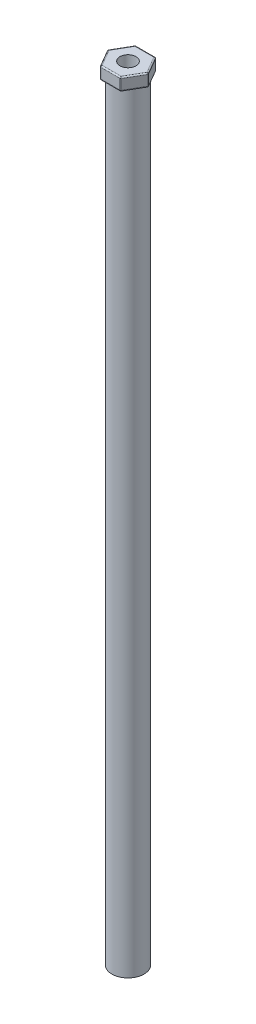
SolidWorks part; units mm, degrees
ref_plane "Front Plane" through (0, 0, 0) normal (0, 0, 1) x (1, 0, 0)
ref_plane "Top Plane" through (0, 0, 0) normal (0, 1, 0) x (1, 0, 0)
ref_plane "Right Plane" through (0, 0, 0) normal (1, 0, 0) x (0, 0, -1)
sketch "Sketch1" plane through (0, 0, 0) normal (0, 1, 0) x (1, 0, 0)
  circle A0 centre (0, 0) radius 6.35
  circle A1 centre (0, 0) radius 3.175
  dimension "D1" = 12.7
extrude "Boss-Extrude1" add sketch "Sketch1" along normal blind 304.8
ref_plane "Plane1" through (0, 152.4, 0) normal (0, 1, 0) x (1, 0, 0)
sketch "Sketch2" plane through (0, 304.8, 0) normal (0, 1, 0) x (1, 0, 0)
  line L1 (-8.0656, 0) -> (-4.0328, -6.985)
  line L2 (-4.0328, -6.985) -> (4.0328, -6.985)
  line L3 (4.0328, -6.985) -> (8.0656, 0)
  line L4 (8.0656, 0) -> (4.0328, 6.985)
  line L5 (4.0328, 6.985) -> (-4.0328, 6.985)
  line L6 (-4.0328, 6.985) -> (-8.0656, 0)
  circle A0 centre (0, 0) radius 6.985 construction
  circle A1 centre (0, 0) radius 3.175
  dimension "D1" = 13.97
extrude "Boss-Extrude2" add sketch "Sketch2" along normal blind 5
fillet "Fillet1" radius 0.5 18 edges at (6.0492, 304.8, -3.4925) (4.0328, 307.3, -6.985) (8.0656, 307.3, 0) (-4.0328, 307.3, -6.985) (-6.0492, 304.8, -3.4925) (-8.0656, 307.3, 0) (-6.0492, 304.8, 3.4925) (-4.0328, 307.3, 6.985) (0, 304.8, 6.985) (6.0492, 304.8, 3.4925) (4.0328, 307.3, 6.985) (6.0492, 309.8, 3.4925) (6.0492, 309.8, -3.4925) (0, 309.8, -6.985) (-6.0492, 309.8, -3.4925) (-6.0492, 309.8, 3.4925) (0, 309.8, 6.985) (0, 304.8, -6.985)
mirror "Mirror1" [suppressed] about plane through (0, 152.4, 0) normal (0, 1, 0)
